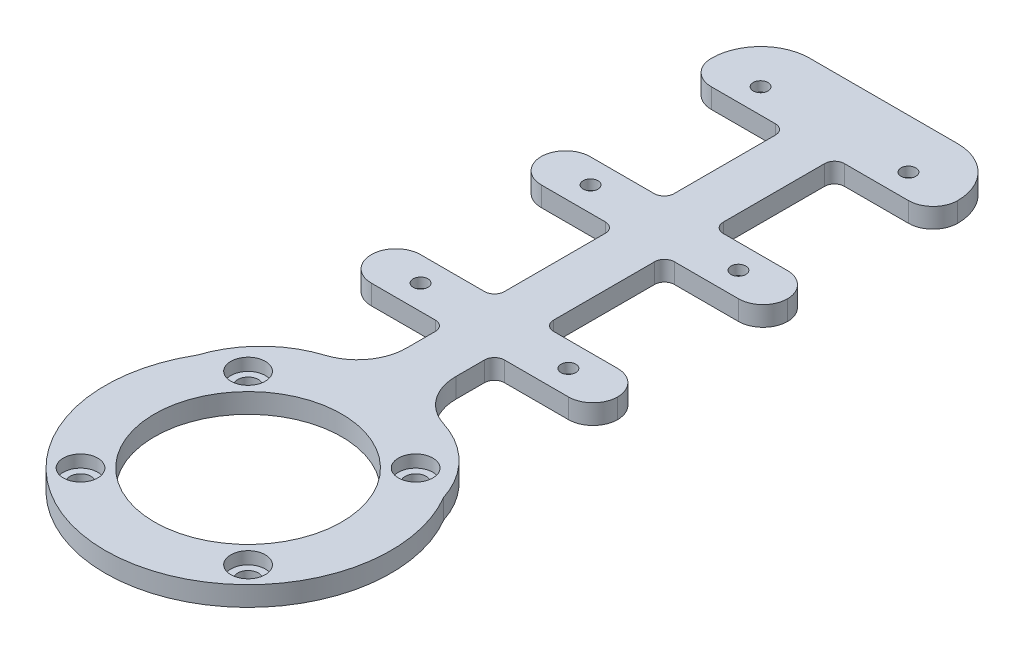
SolidWorks part; units mm, degrees
ref_plane "前视基准面" through (0, 0, 0) normal (0, 0, 1) x (1, 0, 0)
ref_plane "上视基准面" through (0, 0, 0) normal (0, 1, 0) x (1, 0, 0)
ref_plane "右视基准面" through (0, 0, 0) normal (1, 0, 0) x (0, 0, -1)
sketch "草图1" plane through (0, 0, 0) normal (0, 1, 0) x (1, 0, 0)
  circle A0 centre (0, 0) radius 15
  circle A1 centre (0, 0) radius 6
  dimension "D1" = 30
  dimension "D2" = 12
extrude "凸台-拉伸1" add sketch "草图1" along normal blind 2
sketch "草图2" plane through (0, 2, 0) normal (0, 1, 0) x (1, 0, 0)
  circle A0 centre (10, 0) radius 1.5
  dimension "D2" = 3
extrude "切除-拉伸1" cut sketch "草图2" against normal blind 2
pattern_circular "阵列(圆周)1" count 8 over 360 about axis through (0, 2, 0) along (0, -1, 0) of "切除-拉伸1"
sketch "草图3" plane through (0, 2, 0) normal (0, 1, 0) x (1, 0, 0)
  circle A1 centre (0, 0) radius 15
extrude "凸台-拉伸2" add sketch "草图3" along normal blind 2
sketch "草图4" plane through (0, 2, 0) normal (0, -1, 0) x (1, 0, 0)
  circle A0 centre (7.0711, 7.0711) radius 2.75
  dimension "D1" = 5.5
extrude "切除-拉伸2" cut sketch "草图4" against normal blind 2
pattern_circular "阵列(圆周)2" count 8 over 360 about axis through (0, 2, 0) along (0, -1, 0) of "切除-拉伸2"
sketch "草图5" plane through (0, 2, 0) normal (0, -1, 0) x (1, 0, 0)
  circle A0 centre (0, 0) radius 6
extrude "切除-拉伸3" cut sketch "草图5" against normal blind 2
sketch "草图8" plane through (0, 4, 0) normal (0, 1, 0) x (1, 0, 0)
  line L0 (-15, 0) -> (-12.75, 0)
  line L1 (12.75, 0) -> (15, 0)
  line L2 (0, 43) -> (-8, 43)
  line L3 (0, 43) -> (8, 43)
  line L4 (-15, 0) -> (-8, 43)
  line L5 (15, 0) -> (8, 43)
  circle A0 centre (0, 0) radius 15 construction
  arc A1 (12.75, 0) -> (-12.75, 0) centre (0, 0) ccw
  circle A2 centre (10, 0) radius 2.75 construction
  circle A3 centre (10, 0) radius 2.75 construction
  circle A4 centre (-10, 0) radius 2.75 construction
  dimension "D3" = 8
  dimension "D4" = 8
sketch "草图9" plane through (0, 0, 0) normal (0, -1, 0) x (1, 0, 0)
  line L0 (15, 0) -> (8, -43) construction
  line L1 (-15, 0) -> (-8, -43) construction
  line L2 (-15, 0) -> (-15, -5.4278)
  line L3 (-15, -5.4278) -> (-12.9678, -12.4834)
  line L4 (15, 0) -> (15, -5.4278)
  line L5 (15, -5.4278) -> (12.9678, -12.4834)
  arc A0 (-15, 0) -> (15, 0) centre (0, 0) ccw
  arc A1 (-12.9678, -12.4834) -> (12.9678, -12.4834) centre (0, 0) ccw
  dimension "D1" = 18
extrude "凸台-拉伸3" add sketch "草图9" against normal blind 4
extrude "凸台-拉伸4" add sketch "草图8" along normal blind 3
fillet "圆角1" radius 3 2 edges at (13.875, 7, 0) (-13.875, 7, 0)
fillet "圆角2" radius 2 3 edges at (-12.6981, 6.3608, -1.1489) (12.7331, 5.8732, -0.6567) (0, 7, -12.75)
fillet "圆角4" radius 3 2 edges at (-13.9839, 4, -6.2417) (13.9839, 4, -6.2417)
sketch "草图11" plane through (0, 7, 0) normal (0, 1, 0) x (1, 0, 0)
  line L3 (-8, 43) -> (-12.9678, 12.4834) construction
  line L4 (12.9678, 12.4834) -> (8, 43) construction
  line L5 (11.1786, 23.4742) -> (8, 43)
  line L6 (8, 43) -> (-8, 43)
  line L7 (-8, 43) -> (-11.1786, 23.4742)
  arc A1 (-11.1786, 23.4742) -> (11.1786, 23.4742) centre (0, 0) cw
extrude "凸台-拉伸5" add sketch "草图11" along normal blind 1
sketch "草图12" plane through (0, 4, 0) normal (0, -1, 0) x (1, 0, 0)
  line L5 (0, -36.6329) -> (-2.05, -37.8164)
  line L6 (-2.05, -37.8164) -> (-2.05, -40.1836)
  line L7 (-2.05, -40.1836) -> (0, -41.3671)
  line L8 (0, -41.3671) -> (2.05, -40.1836)
  line L9 (2.05, -40.1836) -> (2.05, -37.8164)
  line L10 (2.05, -37.8164) -> (0, -36.6329)
  line L13 (-5, -28.6329) -> (-7.05, -29.8164)
  line L14 (-7.05, -29.8164) -> (-7.05, -32.1836)
  line L15 (-7.05, -32.1836) -> (-5, -33.3671)
  line L16 (-5, -33.3671) -> (-2.95, -32.1836)
  line L17 (-2.95, -32.1836) -> (-2.95, -29.8164)
  line L18 (-2.95, -29.8164) -> (-5, -28.6329)
  line L19 (5, -28.6329) -> (2.95, -29.8164)
  line L20 (2.95, -29.8164) -> (2.95, -32.1836)
  line L21 (2.95, -32.1836) -> (5, -33.3671)
  line L22 (5, -33.3671) -> (7.05, -32.1836)
  line L23 (7.05, -32.1836) -> (7.05, -29.8164)
  line L24 (7.05, -29.8164) -> (5, -28.6329)
  circle A0 centre (0, -39) radius 2.05 construction
  circle A1 centre (-5, -31) radius 2.05 construction
  circle A2 centre (5, -31) radius 2.05 construction
  dimension "D2" = 4.1
  dimension "D5" = 4.1
  dimension "D6" = 4.1
extrude "切除-拉伸4" cut sketch "草图12" against normal blind 2
sketch "草图13" plane through (0, 6, 0) normal (0, -1, 0) x (1, 0, 0)
  circle A0 centre (5, -31) radius 1
  circle A1 centre (-5, -31) radius 1
  circle A2 centre (0, -39) radius 1
  dimension "D1" = 2
  dimension "D2" = 2
  dimension "D3" = 2
extrude "切除-拉伸5" cut sketch "草图13" against normal blind 2
fillet "圆角6" radius 1 1 edges at (0, 8, -26)
fillet "圆角7" radius 1 18 edges at (-1.025, 6, -40.7754) (-2.05, 6, -39) (-1.025, 6, -37.2246) (1.025, 6, -37.2246) (2.05, 6, -39) (1.025, 6, -40.7754) (-2.95, 6, -31) (-3.975, 6, -32.7754) (-6.025, 6, -32.7754) (-7.05, 6, -31) (-3.975, 6, -29.2246) (-6.025, 6, -29.2246) (7.05, 6, -31) (6.025, 6, -32.7754) (3.975, 6, -32.7754) (2.95, 6, -31) (3.975, 6, -29.2246) (6.025, 6, -29.2246)
sketch "草图14" plane through (0, 8, 0) normal (0, 1, 0) x (1, 0, 0)
  circle A0 centre (5, 31) radius 2.3958
  circle A1 centre (-5, 31) radius 3.3415
  circle A2 centre (0, 39) radius 3.655
extrude "凸台-拉伸6" add sketch "草图14" against normal blind 4
sketch "草图15" plane through (0, 8, 0) normal (0, 1, 0) x (1, 0, 0)
  line L3 (-12.5, 43) -> (12.5, 43)
  line L4 (-12.5, 43) -> (-12.5, 35)
  line L5 (12.5, 43) -> (12.5, 35)
  line L6 (-12.5, 35) -> (12.5, 35)
  line L7 (-12.5, 43) -> (12.5, 35) construction
  line L8 (12.5, 43) -> (-12.5, 35) construction
extrude "凸台-拉伸7" add sketch "草图15" against normal blind 4
sketch "草图16" plane through (0, 8, 0) normal (0, 1, 0) x (1, 0, 0)
  circle A0 centre (10.5, 39) radius 1
  circle A1 centre (-10.5, 39) radius 1
  dimension "D4" = 2
  dimension "D5" = 2
extrude "切除-拉伸6" cut sketch "草图16" against normal blind 4
sketch "草图17" plane through (0, 4, 0) normal (0, -1, 0) x (1, 0, 0)
  line L1 (10.5, -41.3671) -> (12.55, -40.1836)
  line L2 (12.55, -40.1836) -> (12.55, -37.8164)
  line L3 (12.55, -37.8164) -> (10.5, -36.6329)
  line L4 (10.5, -36.6329) -> (8.45, -37.8164)
  line L5 (8.45, -37.8164) -> (8.45, -40.1836)
  line L6 (8.45, -40.1836) -> (10.5, -41.3671)
  line L7 (-10.5, -41.3671) -> (-8.45, -40.1836)
  line L8 (-8.45, -40.1836) -> (-8.45, -37.8164)
  line L9 (-8.45, -37.8164) -> (-10.5, -36.6329)
  line L10 (-10.5, -36.6329) -> (-12.55, -37.8164)
  line L11 (-12.55, -37.8164) -> (-12.55, -40.1836)
  line L12 (-12.55, -40.1836) -> (-10.5, -41.3671)
  circle A0 centre (10.5, -39) radius 2.05 construction
  circle A1 centre (-10.5, -39) radius 2.05 construction
  dimension "D1" = 4.1
  dimension "D2" = 4.1
extrude "切除-拉伸7" cut sketch "草图17" against normal blind 2.5
sketch "草图18" plane through (-12.5, 0, 0) normal (-1, 0, 0) x (0, 0, 1)
  line L0 (-43, 8) -> (-43, 4)
  line L1 (-43, 8) -> (-35, 8)
  line L2 (-43, 4) -> (-35, 4)
  line L3 (-35, 8) -> (-35, 4)
  dimension "D1" = 8
extrude "凸台-拉伸8" add sketch "草图18" along normal blind 2
sketch "草图19" plane through (12.5, 0, 0) normal (1, 0, 0) x (0, 0, -1)
  line L0 (35, 4) -> (35, 8)
  line L1 (35, 4) -> (43, 4)
  line L2 (35, 8) -> (43, 8)
  line L3 (43, 4) -> (43, 8)
  dimension "D1" = 8
extrude "凸台-拉伸9" add sketch "草图19" along normal blind 2
fillet "圆角9" radius 1 12 edges at (11.5, 6.5, -37.2102) (12.5, 6.5, -39) (11.5, 6.5, -40.7898) (9.475, 6.5, -40.7754) (8.45, 6.5, -39) (9.475, 6.5, -37.2246) (-9.475, 6.5, -40.7754) (-8.45, 6.5, -39) (-9.475, 6.5, -37.2246) (-11.5, 6.5, -37.2102) (-12.5, 6.5, -39) (-11.5, 6.5, -40.7898)
fillet "圆角10" radius 4 4 edges at (14.5, 6, -35) (14.5, 6, -43) (-14.5, 6, -35) (-14.5, 6, -43)
sketch "草图20" plane through (0, 0, 0) normal (0, 1, 0) x (1, 0, 0)
  circle A0 centre (50.3278, 0) radius 19
  circle A1 centre (50.3278, 0) radius 29
  circle A2 centre (33.3278, 17) radius 1.5
  circle A3 centre (67.3278, 17) radius 1.5
  circle A4 centre (67.3278, -17) radius 1.5
  circle A5 centre (33.3278, -17) radius 1.5
  dimension "D1" = 38
  dimension "D2" = 10
  dimension "D9" = 3
  dimension "D10" = 3
  dimension "D11" = 3
  dimension "D12" = 3
  dimension "D5" = 34
  dimension "D7" = 34
  dimension "D8" = 34
extrude "凸台-拉伸11" add sketch "草图20" along normal blind 4 separate body
sketch "草图23" plane through (0, 4, 0) normal (0, 1, 0) x (1, 0, 0)
  circle A0 centre (33.3278, 17) radius 2.75
  dimension "D1" = 5.5
extrude "切除-拉伸9" cut sketch "草图23" against normal blind 1
pattern_circular "阵列(圆周)5" count 4 over 360 about axis through (50.3278, 4, 0) along (0, -1, 0) of "切除-拉伸9"
sketch "草图24" plane through (0, 0, 0) normal (0, 1, 0) x (1, 0, 0)
  line L0 (25.3278, 129) -> (25.3278, 13.9125)
  line L1 (75.3278, 129) -> (75.3278, 13.9125)
  line L2 (25.3278, 13.9125) -> (31.7041, 20.2888)
  line L3 (31.7041, 20.2888) -> (45.6953, 26.2153)
  line L4 (45.6953, 26.2153) -> (61.6544, 25.3078)
  line L5 (61.6544, 25.3078) -> (69.4628, 20.2888)
  line L6 (69.4628, 20.2888) -> (75.3278, 13.9125)
  line L8 (50.3278, 129) -> (25.3278, 129)
  line L9 (50.3278, 129) -> (75.3278, 129)
  circle A0 centre (35.3278, 50) radius 1.5
  circle A1 centre (65.3278, 50) radius 1.5
  circle A2 centre (35.3278, 119) radius 1.5
  circle A3 centre (65.3278, 119) radius 1.5
  dimension "D7" = 3
  dimension "D8" = 3
  dimension "D9" = 3
  dimension "D10" = 3
  dimension "D11" = 25
  dimension "D12" = 25
extrude "凸台-拉伸12" add sketch "草图24" along normal blind 4
sketch "草图25" plane through (0, 4, 0) normal (0, 1, 0) x (1, 0, 0)
  circle A0 centre (35.3278, 84.5) radius 1.5
  circle A1 centre (65.3278, 84.5) radius 1.5
  circle A2 centre (35.3278, 101.75) radius 1.5
  circle A3 centre (65.3278, 101.75) radius 1.5
  dimension "D1" = 3
  dimension "D2" = 3
  dimension "D3" = 3
  dimension "D4" = 3
extrude "切除-拉伸10" cut sketch "草图25" against normal blind 4
sketch "草图27" plane through (0, 0, 0) normal (0, -1, 0) x (1, 0, 0)
  line L1 (35.3278, -53.2332) -> (38.1278, -51.6166)
  line L2 (38.1278, -51.6166) -> (38.1278, -48.3834)
  line L3 (38.1278, -48.3834) -> (35.3278, -46.7668)
  line L4 (35.3278, -46.7668) -> (32.5278, -48.3834)
  line L5 (32.5278, -48.3834) -> (32.5278, -51.6166)
  line L6 (32.5278, -51.6166) -> (35.3278, -53.2332)
  line L7 (65.3278, -53.2332) -> (68.1278, -51.6166)
  line L8 (68.1278, -51.6166) -> (68.1278, -48.3834)
  line L9 (68.1278, -48.3834) -> (65.3278, -46.7668)
  line L10 (65.3278, -46.7668) -> (62.5278, -48.3834)
  line L11 (62.5278, -48.3834) -> (62.5278, -51.6166)
  line L12 (62.5278, -51.6166) -> (65.3278, -53.2332)
  line L13 (35.3278, -87.7332) -> (38.1278, -86.1166)
  line L14 (38.1278, -86.1166) -> (38.1278, -82.8834)
  line L15 (38.1278, -82.8834) -> (35.3278, -81.2668)
  line L16 (35.3278, -81.2668) -> (32.5278, -82.8834)
  line L17 (32.5278, -82.8834) -> (32.5278, -86.1166)
  line L18 (32.5278, -86.1166) -> (35.3278, -87.7332)
  line L19 (65.3278, -87.7332) -> (68.1278, -86.1166)
  line L20 (68.1278, -86.1166) -> (68.1278, -82.8834)
  line L21 (68.1278, -82.8834) -> (65.3278, -81.2668)
  line L22 (65.3278, -81.2668) -> (62.5278, -82.8834)
  line L23 (62.5278, -82.8834) -> (62.5278, -86.1166)
  line L24 (62.5278, -86.1166) -> (65.3278, -87.7332)
  line L25 (35.3278, -104.9832) -> (38.1278, -103.3666)
  line L26 (38.1278, -103.3666) -> (38.1278, -100.1334)
  line L27 (38.1278, -100.1334) -> (35.3278, -98.5168)
  line L28 (35.3278, -98.5168) -> (32.5278, -100.1334)
  line L29 (32.5278, -100.1334) -> (32.5278, -103.3666)
  line L30 (32.5278, -103.3666) -> (35.3278, -104.9832)
  line L31 (65.3278, -104.9832) -> (68.1278, -103.3666)
  line L32 (68.1278, -103.3666) -> (68.1278, -100.1334)
  line L33 (68.1278, -100.1334) -> (65.3278, -98.5168)
  line L34 (65.3278, -98.5168) -> (62.5278, -100.1334)
  line L35 (62.5278, -100.1334) -> (62.5278, -103.3666)
  line L36 (62.5278, -103.3666) -> (65.3278, -104.9832)
  line L37 (35.3278, -122.2332) -> (38.1278, -120.6166)
  line L38 (38.1278, -120.6166) -> (38.1278, -117.3834)
  line L39 (38.1278, -117.3834) -> (35.3278, -115.7668)
  line L40 (35.3278, -115.7668) -> (32.5278, -117.3834)
  line L41 (32.5278, -117.3834) -> (32.5278, -120.6166)
  line L42 (32.5278, -120.6166) -> (35.3278, -122.2332)
  line L43 (65.3278, -122.2332) -> (68.1278, -120.6166)
  line L44 (68.1278, -120.6166) -> (68.1278, -117.3834)
  line L45 (68.1278, -117.3834) -> (65.3278, -115.7668)
  line L46 (65.3278, -115.7668) -> (62.5278, -117.3834)
  line L47 (62.5278, -117.3834) -> (62.5278, -120.6166)
  line L48 (62.5278, -120.6166) -> (65.3278, -122.2332)
  circle A0 centre (35.3278, -50) radius 2.8 construction
  circle A1 centre (65.3278, -50) radius 2.8 construction
  circle A2 centre (35.3278, -84.5) radius 2.8 construction
  circle A3 centre (65.3278, -84.5) radius 2.8 construction
  circle A4 centre (35.3278, -101.75) radius 2.8 construction
  circle A5 centre (65.3278, -101.75) radius 2.8 construction
  circle A6 centre (35.3278, -119) radius 2.8 construction
  circle A7 centre (65.3278, -119) radius 2.8 construction
  dimension "D1" = 5.6
  dimension "D2" = 5.6
  dimension "D3" = 5.6
  dimension "D4" = 5.6
  dimension "D5" = 5.6
  dimension "D6" = 5.6
  dimension "D7" = 5.6
  dimension "D8" = 5.6
extrude "切除-拉伸11" cut sketch "草图27" against normal blind 2
fillet "圆角11" radius 10 2 edges at (75.3278, 2, -129) (25.3278, 2, -129)
sketch "草图28" plane through (0, 8, 0) normal (0, 1, 0) x (1, 0, 0)
  line L0 (-78.5374, 131.6164) -> (-78.5374, -19.4455)
  line L1 (-78.5374, 131.6164) -> (17.3977, 131.6164)
  line L2 (-78.5374, -19.4455) -> (17.3977, -19.4455)
  line L3 (17.3977, 131.6164) -> (17.3977, -19.4455)
  line L4 (-78.5374, 131.6164) -> (17.3977, -19.4455) construction
  line L5 (-78.5374, -19.4455) -> (17.3977, 131.6164) construction
  point P1 (-30.5699, 56.0854)
extrude "切除-拉伸12" cut sketch "草图28" against normal blind 10
sketch "草图29" plane through (0, 4, 0) normal (0, 1, 0) x (1, 0, 0)
  line L3 (75.3278, 114) -> (55.3278, 114)
  line L4 (25.3278, 114.0029) -> (4.6209, 114.0029)
  line L5 (25.3278, 114.0029) -> (45.3278, 114.0029)
  line L6 (25.3278, 119) -> (25.3278, 14.6969) construction
  line L7 (45.3278, 114.0029) -> (45.3278, 106.937)
  line L8 (45.3278, 106.937) -> (25.3278, 106.937)
  line L9 (25.3278, 106.937) -> (25.3278, 96.75)
  line L10 (25.3278, 96.75) -> (45.3278, 96.75)
  line L11 (45.3278, 96.75) -> (45.3278, 89.426)
  line L12 (45.3278, 89.426) -> (25.3278, 89.426)
  line L13 (25.3278, 89.426) -> (25.3278, 79.5)
  line L14 (25.3278, 79.5) -> (45.3278, 79.5)
  line L15 (45.3278, 79.5) -> (45.3278, 55)
  line L16 (45.3278, 55) -> (25.3278, 55)
  line L17 (25.3278, 55) -> (25.3278, 45)
  line L18 (25.3278, 45) -> (45.3278, 45)
  line L19 (45.3278, 45) -> (45.3278, 28.5657)
  line L20 (45.3278, 28.5657) -> (25.3278, 28.5657)
  line L21 (75.3278, 14.6969) -> (75.3278, 119) construction
  line L22 (55.3278, 114) -> (55.3278, 106.75)
  line L23 (55.3278, 106.75) -> (75.3278, 106.75)
  line L24 (75.3278, 106.75) -> (75.3278, 96.75)
  line L25 (75.3278, 96.75) -> (55.3278, 96.75)
  line L26 (55.3278, 96.75) -> (55.3278, 89.426)
  line L27 (55.3278, 89.426) -> (75.3278, 89.426)
  line L28 (75.3278, 89.426) -> (75.3278, 79.5)
  line L29 (75.3278, 79.5) -> (55.3278, 79.5)
  line L30 (55.3278, 79.5) -> (55.3278, 55)
  line L31 (55.3278, 55) -> (75.3278, 55)
  line L32 (75.3278, 55) -> (75.3278, 45)
  line L33 (75.3278, 45) -> (55.3278, 45)
  line L34 (55.3278, 45) -> (55.3278, 28.5657)
  line L35 (55.3278, 28.5657) -> (75.3278, 28.5657)
  line L36 (4.6209, 114.0029) -> (4.6209, 28.5657)
  line L37 (4.6209, 28.5657) -> (25.3278, 28.5657)
  line L38 (75.3278, 114) -> (112.0768, 114)
  line L39 (112.0768, 114) -> (109.7975, 28.5657)
  line L40 (109.7975, 28.5657) -> (75.3278, 28.5657)
extrude "切除-拉伸13" cut sketch "草图29" against normal blind 10
fillet "圆角12" radius 20 2 edges at (25.3278, 2, -28.5657) (75.3278, 2, -28.5657)
fillet "圆角13" radius 10 2 edges at (45.3278, 2, -28.5657) (55.3278, 2, -28.5657)
fillet "圆角15" radius 5 14 edges at (25.3278, 2, -45) (25.3278, 2, -55) (25.3278, 2, -79.5) (25.3278, 2, -89.426) (25.3278, 2, -96.75) (25.3278, 2, -106.937) (25.3278, 2, -114.0029) (75.3278, 2, -55) (75.3278, 2, -45) (75.3278, 2, -79.5) (75.3278, 2, -89.426) (75.3278, 2, -106.75) (75.3278, 2, -96.75) (75.3278, 2, -114)
fillet "圆角16" radius 2 14 edges at (45.3278, 2, -106.937) (45.3278, 2, -114.0029) (45.3278, 2, -96.75) (45.3278, 2, -89.426) (45.3278, 2, -55) (45.3278, 2, -79.5) (45.3278, 2, -45) (55.3278, 2, -55) (55.3278, 2, -45) (55.3278, 2, -79.5) (55.3278, 2, -96.75) (55.3278, 2, -89.426) (55.3278, 2, -106.75) (55.3278, 2, -114)
fillet "圆角17" radius 1 4 edges at (64.5778, 3, -17) (33.3278, 3, -14.25) (36.0778, 3, 17) (67.3278, 3, 14.25)
fillet "圆角18" radius 1 48 edges at (66.7278, 2, -116.5751) (63.9278, 2, -121.4249) (68.1278, 2, -119) (66.7278, 2, -121.4249) (62.5278, 2, -119) (63.9278, 2, -116.5751) (32.5278, 2, -119) (33.9278, 2, -116.5751) (36.7278, 2, -116.5751) (38.1278, 2, -119) (36.7278, 2, -121.4249) (33.9278, 2, -121.4249) (33.9278, 2, -104.1749) (63.9278, 2, -104.1749) (33.9278, 2, -86.9249) (63.9278, 2, -86.9249) (36.7278, 2, -104.1749) (38.1278, 2, -101.75) (66.7278, 2, -104.1749) (68.1278, 2, -101.75) (36.7278, 2, -86.9249) (38.1278, 2, -84.5) (66.7278, 2, -86.9249) (68.1278, 2, -84.5) (62.5278, 2, -101.75) (66.7278, 2, -99.3251) (63.9278, 2, -99.3251) (36.7278, 2, -99.3251) (62.5278, 2, -84.5) (63.9278, 2, -82.0751) (66.7278, 2, -82.0751) (36.7278, 2, -82.0751) (32.5278, 2, -101.75) (33.9278, 2, -99.3251) (32.5278, 2, -84.5) (33.9278, 2, -82.0751) (63.9278, 2, -47.5751) (66.7278, 2, -47.5751) (62.5278, 2, -50) (63.9278, 2, -52.4249) (66.7278, 2, -52.4249) (68.1278, 2, -50) (36.7278, 2, -52.4249) (33.9278, 2, -52.4249) (32.5278, 2, -50) (33.9278, 2, -47.5751) (36.7278, 2, -47.5751) (38.1278, 2, -50)
sketch "草图30" plane through (0, 4, 0) normal (0, 1, 0) x (1, 0, 0)
  circle A0 centre (67.3278, 17) radius 2.1
  circle A1 centre (33.3278, 17) radius 2.1
  circle A2 centre (33.3278, -17) radius 2.1
  circle A3 centre (67.3278, -17) radius 2.1
  dimension "D1" = 4.2
  dimension "D2" = 4.2
  dimension "D3" = 4.2
  dimension "D4" = 4.2
extrude "切除-拉伸14" cut sketch "草图30" against normal blind 10
sketch "草图31" plane through (0, 4, 0) normal (0, 1, 0) x (1, 0, 0)
  circle A0 centre (67.3278, 17) radius 3.5
  circle A1 centre (33.3278, 17) radius 3.5
  circle A2 centre (33.3278, -17) radius 3.5
  circle A3 centre (67.3278, -17) radius 3.5
  dimension "D1" = 7
  dimension "D2" = 7
  dimension "D3" = 7
  dimension "D4" = 7
extrude "切除-拉伸15" cut sketch "草图31" against normal blind 2.5
sketch "草图32" plane through (0, 0, 0) normal (0, -1, 0) x (1, 0, 0)
  line L0 (45.3278, -110.47) -> (45.3278, -93.088)
  line L1 (45.3278, -108.937) -> (45.3278, -112.0029) construction
  line L2 (45.3278, -91.426) -> (45.3278, -94.75) construction
  line L3 (45.3278, -93.088) -> (23.4541, -93.088)
  line L4 (23.4541, -93.088) -> (24.0975, -110.47)
  line L5 (24.0975, -110.47) -> (45.3278, -110.47)
  line L6 (55.3278, -110.375) -> (77.1344, -110.375)
  line L7 (55.3278, -112) -> (55.3278, -108.75) construction
  line L8 (77.1344, -110.375) -> (76.5223, -93.8369)
  line L9 (76.5223, -93.8369) -> (55.3278, -93.088)
  line L10 (55.3278, -94.75) -> (55.3278, -91.426) construction
  line L11 (55.3278, -93.088) -> (55.3278, -110.375)
extrude "切除-拉伸16" cut sketch "草图32" against normal blind 50
